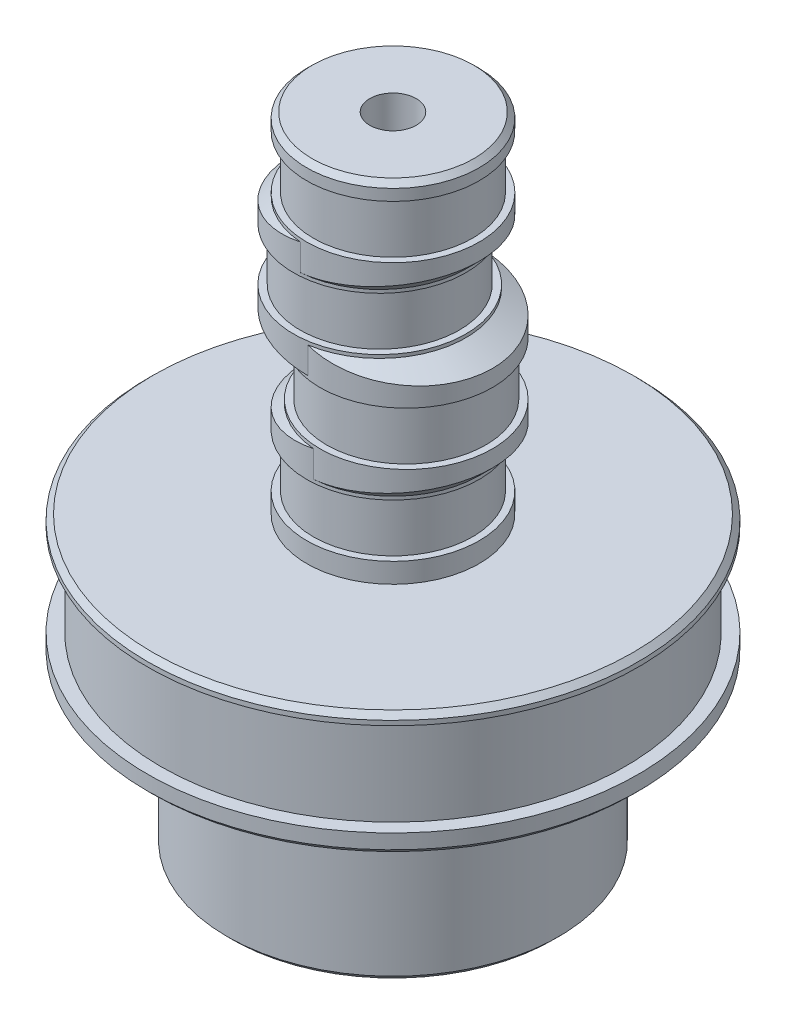
SolidWorks part; units mm, degrees
ref_plane "Front Plane" through (0, 0, 0) normal (0, 0, 1) x (1, 0, 0)
ref_plane "Top Plane" through (0, 0, 0) normal (0, 1, 0) x (1, 0, 0)
ref_plane "Right Plane" through (0, 0, 0) normal (1, 0, 0) x (0, 0, -1)
ref_axis "Axis1" through (0, 25.7, 0) along (0, -1, 0)
sketch "Sketch1" plane through (0, 0, 0) normal (0, 1, 0) x (1, 0, 0)
  circle A0 centre (0, 0) radius 18.5
  dimension "D1" = 37
extrude "Boss-Extrude1" add sketch "Sketch1" along normal mid plane 9.5
sketch "Sketch2" plane through (0, -4.75, 0) normal (0, -1, 0) x (1, 0, 0)
  circle A0 centre (0, 0) radius 17.5
  dimension "D1" = 35
extrude "Cut-Extrude-Thin1" cut sketch "Sketch2" against normal blind 7 from offset 1.5 thin offset against normal yes thin type one direction wall 10
sketch "Sketch8" plane through (0, 4.75, 0) normal (0, 1, 0) x (1, 0, 0)
  circle A0 centre (0, 0) radius 6.5
  dimension "D1" = 13
extrude "Boss-Extrude4" add sketch "Sketch8" along normal blind 6.5
ref_plane "Plane3" through (0, 8, 0) normal (0, 1, 0) x (1, 0, 0)
sketch "Sketch9" plane through (0, 8, 0) normal (0, 1, 0) x (1, 0, 0)
  circle A0 centre (0, 0) radius 6
  dimension "D1" = 12
extrude "Cut-Extrude-Thin4" cut sketch "Sketch9" against normal mid plane 4 thin thin type one direction wall 10
sketch "Sketch3" plane through (0, 11.25, 0) normal (0, 1, 0) x (1, 0, 0)
  line L0 (0, 0) -> (1, 0) construction
  circle A0 centre (1, 0) radius 6.5
  dimension "D2" = 13
  dimension "D1" = 1
extrude "Boss-Extrude2" add sketch "Sketch3" along normal blind 6.5
sketch "Sketch4" plane through (0, 17.75, 0) normal (0, 1, 0) x (1, 0, 0)
  line L0 (-1, 0) -> (0, 0) construction
  line L1 (0, 0) -> (1, 0) construction
  circle A0 centre (-1, 0) radius 6.5
  circle A1 centre (1, 0) radius 6.5 construction
extrude "Boss-Extrude3" add sketch "Sketch4" along normal blind 6.5
ref_plane "Plane1" through (0, 14.5, 0) normal (0, 1, 0) x (1, 0, 0)
sketch "Sketch5" plane through (0, 14.5, 0) normal (0, 1, 0) x (1, 0, 0)
  circle A0 centre (1, 0) radius 6
  dimension "D1" = 12
extrude "Cut-Extrude-Thin2" cut sketch "Sketch5" against normal mid plane 4 thin thin type one direction wall 10
ref_plane "Plane2" through (0, 21, 0) normal (0, -1, 0) x (-1, 0, 0)
sketch "Sketch7" plane through (0, 21, 0) normal (0, -1, 0) x (-1, 0, 0)
  circle A0 centre (1, 0) radius 6
  circle A1 centre (1, 0) radius 6.5 construction
  dimension "D1" = 12
extrude "Cut-Extrude-Thin3" cut sketch "Sketch7" against normal mid plane 4 thin thin type one direction wall 10
sketch "Sketch10" plane through (0, 4.75, 0) normal (0, 1, 0) x (1, 0, 0)
  circle A1 centre (0, 0) radius 6.5 construction
  circle A2 centre (0, 0) radius 6.5
  circle A3 centre (0, 0) radius 18.5 construction
  circle A4 centre (0, 0) radius 18.5
extrude "Cut-Extrude1" cut sketch "Sketch10" against normal blind 0.25
sketch "Sketch11" plane through (0, 24.25, 0) normal (0, 1, 0) x (1, 0, 0)
  circle A0 centre (0, 0) radius 6.5
  circle A1 centre (-1, 0) radius 6.5 construction
extrude "Boss-Extrude5" add sketch "Sketch11" along normal blind 6.5
ref_plane "Plane4" through (0, 27.5, 0) normal (0, 1, 0) x (1, 0, 0)
sketch "Sketch12" plane through (0, 27.5, 0) normal (0, 1, 0) x (1, 0, 0)
  circle A0 centre (0, 0) radius 6
  dimension "D1" = 12
extrude "Cut-Extrude-Thin5" cut sketch "Sketch12" against normal mid plane 4 thin thin type one direction wall 10
chamfer "Chamfer1" distance 1 angle 45 2 edges at (-6.5, 24.25, 0) (-5.5, 11.25, 0)
chamfer "Chamfer2" distance 1 angle 45 2 edges at (6.5, 11.25, 0) (5.5, 24.25, 0)
chamfer "Chamfer3" distance 1 distance2 2 1 edges at (-5.5, 17.75, 0) first distance on face at (1, 16.5, 6.5)
chamfer "Chamfer4" distance 2 distance2 1 1 edges at (5.5, 17.75, 0) first distance on face at (6.5, 17.75, 0)
sketch "Sketch13" plane through (0, -4.75, 0) normal (0, -1, 0) x (1, 0, 0)
  circle A0 centre (0, 0) radius 12.5
  dimension "D1" = 25
extrude "Boss-Extrude6" add sketch "Sketch13" along normal blind 12.5
sketch "Sketch14" plane through (0, -17.25, 0) normal (0, -1, 0) x (1, 0, 0)
  line L1 (4.1858, 7.25) -> (-4.1858, 7.25)
  line L2 (-4.1858, 7.25) -> (-8.3716, 0)
  line L3 (-8.3716, 0) -> (-4.1858, -7.25)
  line L4 (-4.1858, -7.25) -> (4.1858, -7.25)
  line L5 (4.1858, -7.25) -> (8.3716, 0)
  line L6 (8.3716, 0) -> (4.1858, 7.25)
  circle A0 centre (0, 0) radius 7.25 construction
  dimension "D1" = 14.5
extrude "Cut-Extrude3" cut sketch "Sketch14" against normal blind 14 draft 5
chamfer "Chamfer5" distance 0.4 angle 45 4 edges at (0, 30.75, 6.5) (0, 4.5, 18.5) (0, -17.25, -12.5) (0, -4.75, 18.5)
sketch "Sketch15" plane through (0, -3.25, 0) normal (0, -1, 0) x (1, 0, 0)
  circle A0 centre (0, 0) radius 1.75
  dimension "D1" = 3.5
extrude "Cut-Extrude4" cut sketch "Sketch15" against normal through all both and the other way through all
sketch "Sketch16" plane through (0, -3.25, 0) normal (0, -1, 0) x (1, 0, 0)
  circle A0 centre (0, 0) radius 2.35
  dimension "D1" = 4.7
extrude "Cut-Extrude5" cut sketch "Sketch16" against normal blind 4
equation "\"RotorRadius\"= 25mm"
equation "\"Eccentricity\"= 1.00mm"
equation "\"RollerRadius\"= 1.5mm"
equation "\"GearRatio\"= 20"
equation "\"RollerCount\"=\"GearRatio\" + 1"
equation "\"RotorThickness\"= 6mm"
equation "\"OutputRollerRadius\"= 1.5mm"
equation "\"OutputRollerCount\"= 6"
equation "\"OutputRollerHoleCircleRadius\"=\"RotorRadius\"- 4 * \"OutputRollerRadius\""
equation "\"RotorGap\"= 0.5mm"
equation "\"D1@Sketch3\"=\"Eccentricity\""
